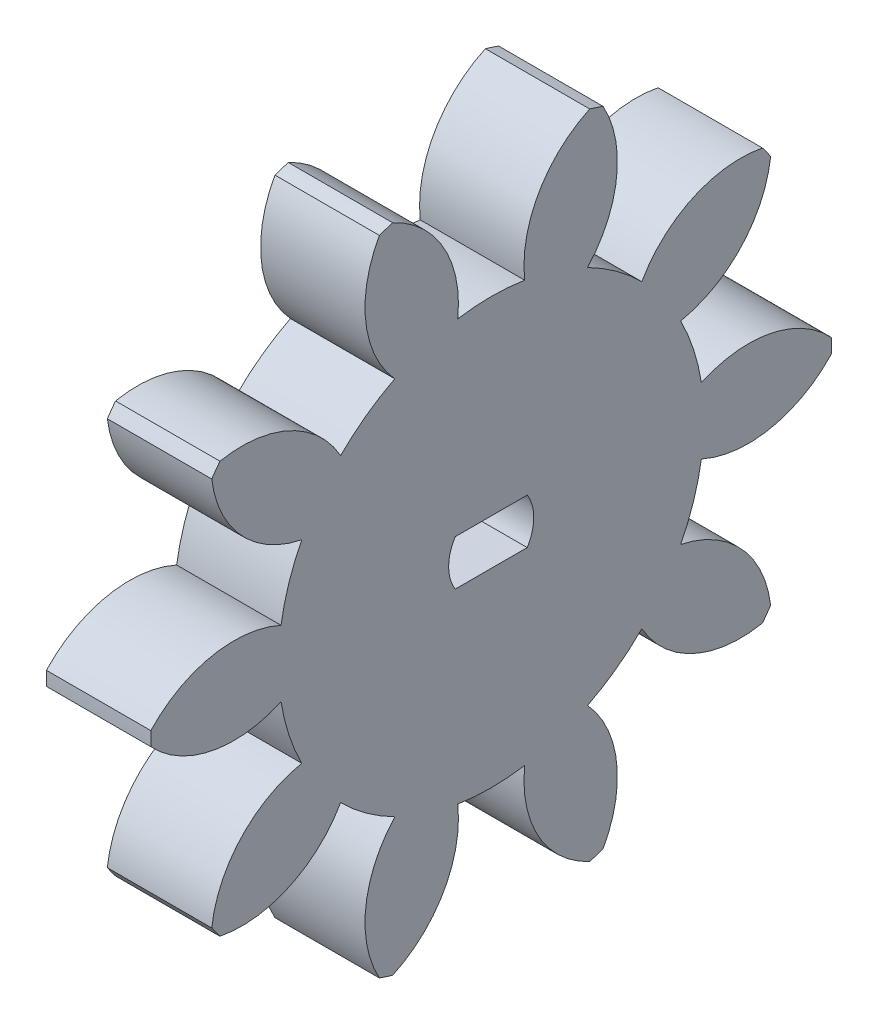
SolidWorks part; units mm, degrees
ref_plane "Plane1" through (0, 0, 0) normal (0, 0, 1) x (1, 0, 0)
ref_plane "Plane2" through (0, 0, 0) normal (0, 1, 0) x (1, 0, 0)
ref_plane "Plane3" through (0, 0, 0) normal (1, 0, 0) x (0, 0, -1)
sketch "HoldingSke" plane through (0, 0, 0) normal (0, 1, 0) x (1, 0, 0)
  line L0 (0, 0) -> (200.1129, -35.2853)
  line L1 (-15, 0) -> (100, 0) construction
  line L2 (0, 0) -> (-2.1039, 2.3779)
  line L3 (0, 0) -> (-11.863, 4.5341)
  line L4 (0, 0) -> (8.5048, 1.4996)
  line L5 (0, 0) -> (-47.5972, -17.7524)
  line L6 (0, 0) -> (-4.8428, -3.2675)
  line L7 (-2.1039, 2.3779) -> (8.8308, 51.9871)
  line L8 (-76.2, 54.61) -> (-71.1708, 54.61)
  line L9 (-71.009, 38.7566) -> (-53.1078, 45.2721)
  line L10 (-76.2, 71.12) -> (104.1128, 71.12)
  line L11 (0, 0) -> (-5.842, 0)
  line L12 (-76.2, 101.6) -> (-76.0857, 101.6)
  line L13 (24.9733, 27.94) -> (52.9518, 28.4284)
  line L14 (24.9733, 27.94) -> (24.9746, 27.94)
  line L15 (24.9733, 27.94) -> (100.4006, 29.5858)
  circle A0 centre (0, 0) radius 2.3813
  circle A1 centre (0, 0) radius 11.905
  circle A2 centre (0, 0) radius 38.1
  circle A3 centre (0, 0) radius 2.3812
  dimension "Num_teeth" = 10
  dimension "H" = 19.05
  dimension "Pitch_radius" = 180.3128
  dimension "Width" = 5.842
  dimension "Thickness" = 5.842
sketch "BasProSke" plane through (0, 0, 0) normal (0, 1, 0) x (1, 0, 0)
  line L0 (-10, 0) -> (60, 0) construction
  line L1 (0, 0) -> (0, 19.05)
  line L2 (0, 0) -> (5.842, 0)
  line L3 (5.842, 0) -> (5.842, 19.05)
  line L4 (5.842, 19.05) -> (0, 19.05)
  dimension "Thickness" = 5.842
  dimension "Diameter" = 38.1
revolve "Base-Revolve" add sketch "BasProSke" angle 360 about L0
sketch "TooCutSke" plane through (0, 0, 0) normal (1, 0, 0) x (0, 0, -1)
  line L1 (0, 0) -> (0, 107) construction
  line L2 (0, 0) -> (-2.683, 15.6466) construction
  line L3 (0, 0) -> (-9.7093, 29.8821) construction
  line L4 (-2.683, 15.6466) -> (-4.8546, 14.941) construction
  arc A0 (1.8735, 11.7566) -> (-1.8735, 11.7566) centre (0, 0) ccw
  arc A1 (5.5485, 18.2506) -> (-5.5485, 18.2506) centre (0, 0) ccw
  circle A2 centre (0, 0) radius 15.875 construction
  circle A3 centre (0, 0) radius 14.9176 construction
  arc A4 (-1.8735, 11.7566) -> (-5.5485, 18.2506) centre (-8.183, 12.4729) ccw
  arc A5 (5.5485, 18.2506) -> (1.8735, 11.7566) centre (8.183, 12.4729) ccw
extrude "ToothCut" cut sketch "TooCutSke" along normal through all
fillet "Breaks" [suppressed] radius 0.0635 tangent propagation no
fillet "RootFillets" [suppressed] radius 0.795
pattern_circular "TeethCuts" count 10 every 36 about axis through (-10, 0, 0) along (1, 0, 0) of "ToothCut", "RootFillets", "Breaks"
sketch "HubNeaOneSke" plane through (0, 0, 0) normal (-1, 0, 0) x (0, 0, 1)
  circle A0 centre (0, 0) radius 11.905
  dimension "Diameter" = 23.81
extrude "HubNearOne" [suppressed] add sketch "HubNeaOneSke" along normal blind 44.9581
sketch "HubNeaBotSke" plane through (0, 0, 0) normal (-1, 0, 0) x (0, 0, 1)
  circle A0 centre (0, 0) radius 11.905
  dimension "Diameter" = 23.81
extrude "HubNearBoth" [suppressed] add sketch "HubNeaBotSke" along normal blind 22.479
ref_plane "FarPln" through (5.842, 0, 0) normal (1, 0, 0) x (0, 0, -1)
sketch "HubFarSke" plane through (5.842, 0, 0) normal (1, 0, 0) x (0, 0, -1)
  circle A0 centre (0, 0) radius 11.905
  dimension "Diameter" = 23.81
extrude "HubFar" [suppressed] add sketch "HubFarSke" along normal blind 22.479
sketch "BorSke" plane through (0, 0, 0) normal (1, 0, 0) x (0, 0, -1)
  circle A0 centre (0, 0) radius 2.3812
  dimension "Diameter" = 4.7625
extrude "Bore" cut sketch "BorSke" along normal mid plane 101.6001
sketch "KeySke" plane through (0, 0, 0) normal (1, 0, 0) x (0, 0, -1)
  line L0 (-0.127, 0) -> (-0.127, 2.648)
  line L1 (-0.127, 2.648) -> (0.127, 2.648)
  line L2 (0.127, 2.648) -> (0.127, 0)
  line L3 (0, 0) -> (0, 34) construction
  line L4 (-0.127, 0) -> (0.127, 0)
  dimension "Width" = 0.254
extrude "Keyway" [suppressed] cut sketch "KeySke" along normal mid plane 101.6001
pattern_circular "Keyway2" [suppressed] count 2 every 90 about axis through (-10, 0, 0) along (1, 0, 0) reverse direction yes
sketch "Sketch1" plane through (5.842, 0, 0) normal (1, 0, 0) x (0, 0, -1)
  line L0 (-2.2215, 1.27) -> (2.2215, 1.27)
  line L1 (-2.2215, -1.27) -> (2.2215, -1.27)
  line L2 (0, 1.27) -> (0, -1.27) construction
  arc A0 (-2.2215, -1.27) -> (2.2215, -1.27) centre (0, 0) ccw
  circle A1 centre (0, 0) radius 2.3812 construction
  arc A2 (2.2215, 1.27) -> (-2.2215, 1.27) centre (0, 0) ccw
  point P9 (0, 0)
  dimension "D1" = 2.54
extrude "Boss-Extrude1" add sketch "Sketch1" against normal up to surface (5.842 mm away) up to face at (0, 0, -2.3812)
equation "' \"Pitch@HoldingSke\" = 4"
equation "' \"Num_teeth@HoldingSke\" = 12"
equation "' \"Ap@HoldingSke\" =  20"
equation "' \"Ap@HoldingSke\" = 20"
equation "' \"Width@HoldingSke\" = 0.5"
equation "' \"Hub_dia@HoldingSke\"= 1"
equation "' \"Hub_dia@HoldingSke\" = 1"
equation "' \"Overall_len@HoldingSke\" = 1.0"
equation "' \"Bore@HoldingSke\" = 0.75"
equation "' \"T_dim@HoldingSke\" = 0.85"
equation "' \"Width@KeySke\" = 0.25"
equation "' \"Show_teeth@HoldingSke\" = 13"
equation "' \"Backlash@HoldingSke\" = 0.009"
equation "' \"Addendum_fac@HoldingSke\" = 1.0"
equation "' \"Dedendum_fac@HoldingSke\" = 1.25"
equation "' \"Dedendum_add@HoldingSke\" = 0.00005"
equation "' \"Clearance_fac@HoldingSke\" = 0.25"
equation "' \"Pitch@HoldingSke\" = 0.5"
equation "' \"Num_teeth@HoldingSke\" = 23"
equation "' \"Show_teeth@HoldingSke\" = 23"
equation "' \"Backlash@HoldingSke\" = 0.0375"
equation "\"Overcut_dia@TooCutSke\" = (\"Num_teeth@HoldingSke\" + 2 * \"Addendum_fac@HoldingSke\") / \"Pitch@HoldingSke\" + 0.002"
equation "\"Pitch_dia@TooCutSke\" = \"Num_teeth@HoldingSke\" / \"Pitch@HoldingSke\""
equation "\"Base_dia@TooCutSke\" = \"Num_teeth@HoldingSke\" / \"Pitch@HoldingSke\" * cos((\"Ap@HoldingSke\"  * 3.14159265 / 180))"
equation "\"Root_dia@TooCutSke\" = (\"Num_teeth@HoldingSke\" + 2) / \"Pitch@HoldingSke\" - 2 * (\"Addendum_fac@HoldingSke\" + \"Dedendum_fac@HoldingSke\") / \"Pitch@HoldingSke\" - \"Dedendum_add@HoldingSke\" * 2"
equation "\"Half_ang@TooCutSke\" = 180 / \"Num_teeth@HoldingSke\""
equation "\"Half_CT@TooCutSke\" = \"Num_teeth@HoldingSke\" / \"Pitch@HoldingSke\" * sin((3.14159265 / 2 / \"Num_teeth@HoldingSke\")) / 2 - 7 * \"Backlash@HoldingSke\" / 4"
equation "\"Flank_rad@TooCutSke\" = \"Num_teeth@HoldingSke\" / \"Pitch@HoldingSke\" / 5"
equation "\"Radius@RootFillets\" = \"Clearance_fac@HoldingSke\" / \"Pitch@HoldingSke\" + \"Dedendum_add@HoldingSke\""
equation "\"Break_rad@Breaks\" = 0.02 / \"Pitch@HoldingSke\""
equation "\"Thickness@HoldingSke\" = \"Width@HoldingSke\""
equation "\"OAL@HoldingSke\" = \"Thickness@HoldingSke\""
equation "\"MHD@HoldingSke\" = (\"Num_teeth@HoldingSke\" + 2) / \"Pitch@HoldingSke\" - 2 * (\"Addendum_fac@HoldingSke\" + \"Dedendum_fac@HoldingSke\")  / \"Pitch@HoldingSke\" - \"Dedendum_add@HoldingSke\" * 2"
equation "\"MBD@HoldingSke\" = (\"Num_teeth@HoldingSke\" + 2) / \"Pitch@HoldingSke\" - 2 * (\"Addendum_fac@HoldingSke\" + \"Dedendum_fac@HoldingSke\")  / \"Pitch@HoldingSke\" - \"Dedendum_add@HoldingSke\" * 2 - 0.002"
equation "\"MHD@HoldingSke\" = ((sgn( \"MHD@HoldingSke\" - \"Hub_dia@HoldingSke\" )-1)*( \"MHD@HoldingSke\" - \"Hub_dia@HoldingSke\" ))/-2+ \"Hub_dia@HoldingSke\""
equation "\"MBD@HoldingSke\" = ((sgn( \"MBD@HoldingSke\" - \"Bore@HoldingSke\" )-1)*( \"MBD@HoldingSke\" - \"Bore@HoldingSke\" ))/-2+ \"Bore@HoldingSke\""
equation "\"OAL@HoldingSke\" = ((sgn( \"OAL@HoldingSke\" - \"Overall_len@HoldingSke\" )+1)*( \"OAL@HoldingSke\" - \"Overall_len@HoldingSke\" ))/2 + \"Overall_len@HoldingSke\" + 0.000002"
equation "\"Num_teeth@TeethCuts\" = int( \"Show_teeth@HoldingSke\" ) + 1"
equation "\"Num_teeth@TeethCuts\" = ((sgn( \"Num_teeth@TeethCuts\" - \"Num_teeth@HoldingSke\" )-1)*( \"Num_teeth@TeethCuts\" - \"Num_teeth@HoldingSke\" ))/-2+ \"Num_teeth@HoldingSke\""
equation "\"Num_teeth@TeethCuts\" = ((sgn( \"Num_teeth@TeethCuts\" - 2.0)+1)*( \"Num_teeth@TeethCuts\" - 2.0))/2 +2.0"
equation "\"Angle@TeethCuts\" = 360.0 / \"Num_teeth@HoldingSke\""
equation "\"Diameter@BasProSke\" = (\"Num_teeth@HoldingSke\" + 2 * \"Addendum_fac@HoldingSke\") / \"Pitch@HoldingSke\""
equation "\"Thickness@BasProSke\"  = \"Thickness@HoldingSke\""
equation "' \"Fillet_rad@BasProSke\" =  \"Thickness@HoldingSke\" * 0.05"
equation "' \"Fillet_rad@BasProSke\" = \"Thickness@HoldingSke\" * 0.05"
equation "\"MHD@HoldingSke\" = ((sgn( \"MHD@HoldingSke\" - \"Root_dia@TooCutSke\" )-1)*( \"MHD@HoldingSke\" - \"Root_dia@TooCutSke\" ))/-2+ \"Root_dia@TooCutSke\""
equation "\"Diameter@HubNeaOneSke\" = \"MHD@HoldingSke\""
equation "\"Length@HubNearOne\" = \"OAL@HoldingSke\" - \"Thickness@BasProSke\""
equation "\"Diameter@HubNeaBotSke\" = \"MHD@HoldingSke\""
equation "\"Length@HubNearBoth\" = ( \"OAL@HoldingSke\" - \"Thickness@BasProSke\" ) / 2.0"
equation "\"Thickness@FarPln\" = \"Thickness@BasProSke\""
equation "\"Diameter@HubFarSke\" = \"MHD@HoldingSke\""
equation "\"Length@HubFar\" = ( \"OAL@HoldingSke\" - \"Thickness@BasProSke\" ) / 2.0"
equation "\"Diameter@BorSke\" = \"MBD@HoldingSke\""
equation "\"D1@Bore\" = \"OAL@HoldingSke\" * 2.0"
equation "\"D1@Keyway\" = \"OAL@HoldingSke\" * 2.0"
equation "\"Offset@KeySke\" = \"T_dim@HoldingSke\" - \"MBD@HoldingSke\" / 2.0"
